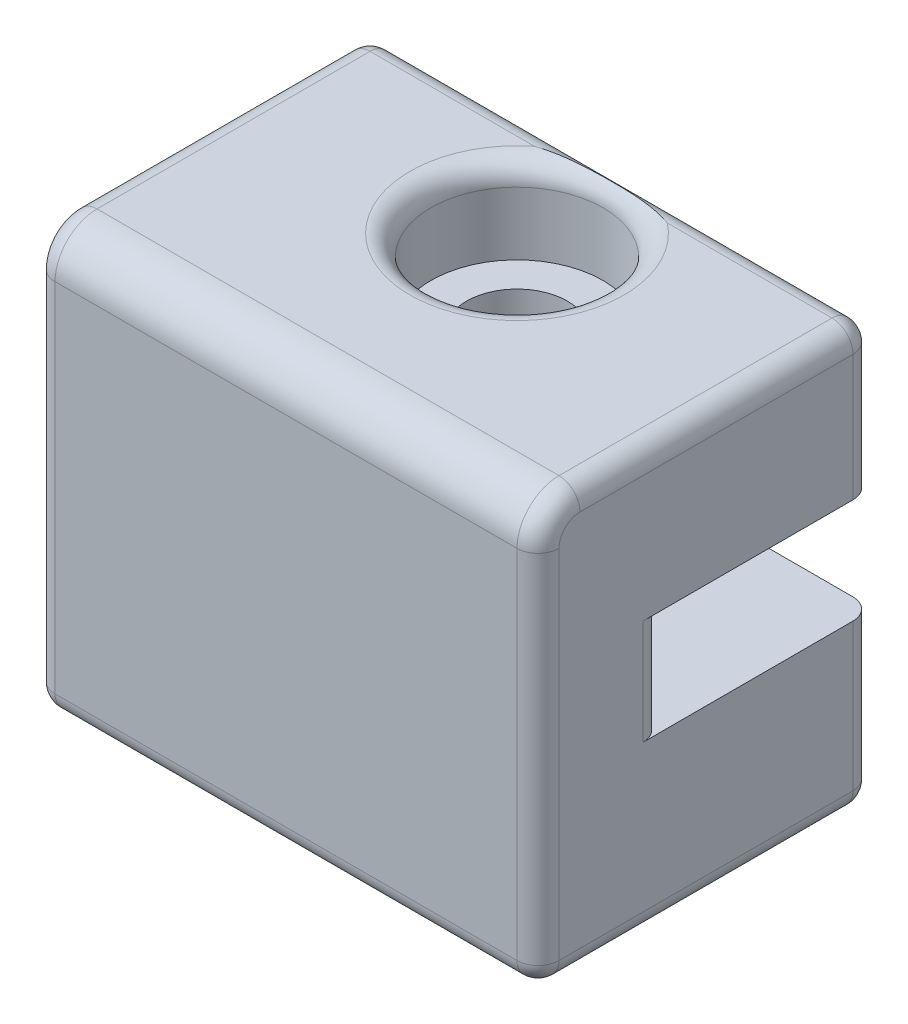
SolidWorks part; units mm, degrees
ref_plane "Front Plane" through (0, 0, 0) normal (0, 0, 1) x (1, 0, 0)
ref_plane "Top Plane" through (0, 0, 0) normal (0, 1, 0) x (1, 0, 0)
ref_plane "Right Plane" through (0, 0, 0) normal (1, 0, 0) x (0, 0, -1)
sketch "Sketch1" plane through (0, 0, 0) normal (0, 1, 0) x (1, 0, 0)
  line L5 (-6, -2.5) -> (6, -2.5)
  line L6 (-6, -2.5) -> (-6, 2.5)
  line L7 (-6, 2.5) -> (6, 2.5)
  line L8 (6, -2.5) -> (6, 2.5)
  line L9 (-6, -2.5) -> (6, 2.5) construction
  line L10 (-6, 2.5) -> (6, -2.5) construction
  point P0 (0, 0)
  dimension "D1" = 12
  dimension "D2" = 5
extrude "Boss-Extrude1" add sketch "Sketch1" along normal blind 4
sketch "Sketch2" plane through (0, 0, 2.5) normal (0, 0, 1) x (1, 0, 0)
  line L0 (6, 4) -> (6, 0) construction
  line L1 (-6, 0) -> (6, 0)
  line L2 (-6, 0) -> (-6, 6.5)
  line L3 (-6, 6.5) -> (6, 6.5)
  line L4 (6, 0) -> (6, 6.5)
  dimension "D1" = 6.5
extrude "Boss-Extrude2" add sketch "Sketch2" along normal blind 3
sketch "Sketch3" plane through (0, 6.5, 0) normal (0, 1, 0) x (1, 0, 0)
  line L1 (-6, -5.5) -> (6, -5.5)
  line L2 (-6, -5.5) -> (-6, 2.5)
  line L3 (-6, 2.5) -> (6, 2.5)
  line L4 (6, -5.5) -> (6, 2.5)
extrude "Boss-Extrude3" add sketch "Sketch3" along normal blind 3.5
sketch "Sketch4" plane through (0, 4, 0) normal (0, 1, 0) x (1, 0, 0)
  line L0 (6, 2.5) -> (-6, -2.5) construction
  line L1 (-6, 2.5) -> (6, -2.5) construction
  circle A0 centre (0, 0) radius 1.2
  dimension "D1" = 2.4
extrude "Cut-Extrude1" cut sketch "Sketch4" against normal blind 5 and the other way blind 7
sketch "Sketch5" plane through (0, 10, 0) normal (0, 1, 0) x (1, 0, 0)
  circle A0 centre (0, 0) radius 2.05
  dimension "D1" = 4.1
extrude "Cut-Extrude2" cut sketch "Sketch5" against normal blind 2
fillet "Fillet3" radius 0.5 8 edges at (-6, 0, 1.5) (0, 0, -2.5) (6, 0, 1.5) (0, 0, 5.5) (-6, 5.25, 2.5) (6, 5.25, 2.5) (-6, 2, -2.5) (6, 2, -2.5)
fillet "Fillet6" radius 1 1 edges at (0, 10, 5.5)
fillet "Fillet7" radius 0.5 12 edges at (5.8536, 0.1464, 5.3536) (6, 4.75, 5.5) (6, 9.7071, 5.2071) (-5.8536, 0.1464, 5.3536) (-6, 4.75, 5.5) (-6, 9.7071, 5.2071) (6, 8.25, -2.5) (6, 10, 1) (0, 10, -2.5) (0, 10, 2.05) (-6, 10, 1) (-6, 8.25, -2.5)
